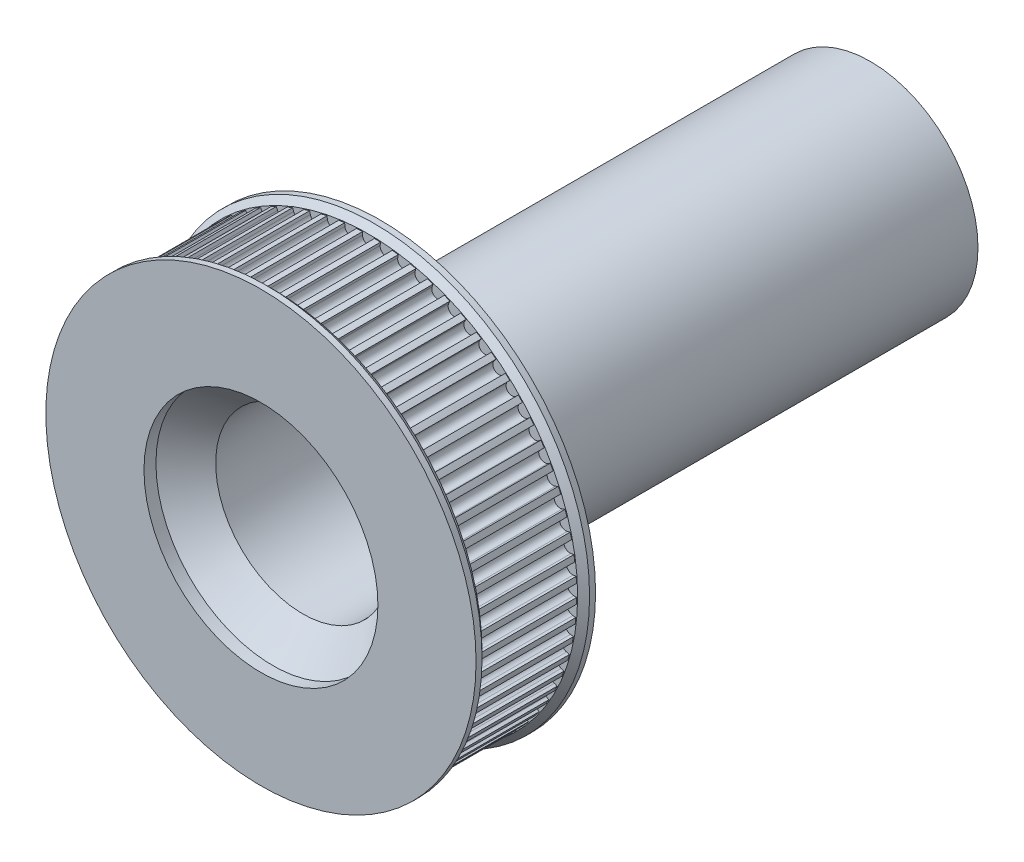
SolidWorks part; units mm, degrees
material "PA Type 6"
ref_plane "Front Plane" through (0, 0, 0) normal (0, 0, 1) x (1, 0, 0)
ref_plane "Top Plane" through (0, 0, 0) normal (0, 1, 0) x (1, 0, 0)
ref_plane "Right Plane" through (0, 0, 0) normal (1, 0, 0) x (0, 0, -1)
sketch "Sketch1" plane through (0, 0, 0) normal (0, 0, 1) x (1, 0, 0)
  circle A0 centre (0, 0) radius 18
extrude "Boss-Extrude1" add sketch "Sketch1" along normal blind 100
sketch "Sketch2" plane through (0, 0, 100) normal (0, 0, 1) x (1, 0, 0)
  circle A0 centre (0, 0) radius 14.576
extrude "Cut-Extrude1" cut sketch "Sketch2" against normal blind 85
sketch "Sketch3" plane through (0, 0, 0) normal (0, 0, -1) x (-1, 0, 0)
  circle A0 centre (0, 0) radius 4.5
  circle A1 centre (0, 0) radius 18 construction
  dimension "D1" = 9
extrude "Cut-Extrude2" cut sketch "Sketch3" against normal blind 60
sketch "Sketch4" plane through (0, 0, 100) normal (0, 0, 1) x (1, 0, 0)
  circle A0 centre (0, 0) radius 14.576
  circle A1 centre (0, 0) radius 34.85
  dimension "D1" = 69.7
extrude "Boss-Extrude2" add sketch "Sketch4" against normal blind 18
sketch "Sketch5" plane through (0, 0, 100) normal (0, 0, 1) x (1, 0, 0)
  circle A0 centre (1.619, -28.1194) radius 3.1814
extrude "Cut-Extrude3" cut sketch "Sketch5" against normal blind 4 from offset 13 offset against normal yes
chamfer "Chamfer2" distance 5 angle 45 1 edges at (14.576, 0, 15)
chamfer "Chamfer3" distance 5 angle 45 1 edges at (14.576, 0, 100)
sketch "Sketch6" plane through (0, 0, 100) normal (0, 0, 1) x (1, 0, 0)
  line L0 (0, 35.6693) -> (0, 34.3375) construction
  line L1 (1, 35.6693) -> (1, 34.3375)
  line L2 (-1, 35.6693) -> (-1, 34.3375)
  arc A0 (1, 35.6693) -> (-1, 35.6693) centre (0, 35.6693) ccw
  arc A1 (-1, 34.3375) -> (1, 34.3375) centre (0, 34.3375) ccw
  point P2 (0, 35.0034)
  dimension "D1" = 1
extrude "Cut-Extrude4" cut sketch "Sketch6" against normal blind 18
pattern_circular "CirPattern1" count 73 over 360 about axis through (0, 0, 100) along (0, 0, 1) of "Cut-Extrude4"
sketch "Sketch7" plane through (0, 0, 100) normal (0, 0, 1) x (1, 0, 0)
  circle A0 centre (0, 0) radius 19.576
  circle A1 centre (0, 0) radius 36
extrude "Boss-Extrude3" add sketch "Sketch7" along normal blind 2
pattern_linear "LPattern1" count 2 spacing 18 along (0, 0, -1) of "Boss-Extrude3"
chamfer "Chamfer4" distance 1 angle 45 2 edges at (36, 0, 100) (36, 0, 84)
sketch "Эскиз1" plane through (0, 0, 82) normal (0, 0, -1) x (-1, 0, 0)
  circle A0 centre (-9.4119, 27.7754) radius 3.5
extrude "Вырез-Вытянуть1" cut sketch "Эскиз1" against normal blind 4
sketch "Эскиз2" plane through (0, 0, 0) normal (0, 0, -1) x (-1, 0, 0)
  line L1 (-2, 8.5265) -> (2, 8.5265)
  line L2 (-2, 8.5265) -> (-2, 0.0452)
  line L3 (-2, 0.0452) -> (2, 0.0452)
  line L4 (2, 8.5265) -> (2, 0.0452)
  line L5 (-2, 8.5265) -> (2, 0.0452) construction
  line L6 (-2, 0.0452) -> (2, 8.5265) construction
  point P0 (0, 4.2859)
  point P5 (0, 0)
  point P6 (0, 3.596)
  dimension "D1" = 4
extrude "Вырез-Вытянуть2" cut sketch "Эскиз2" against normal blind 12
